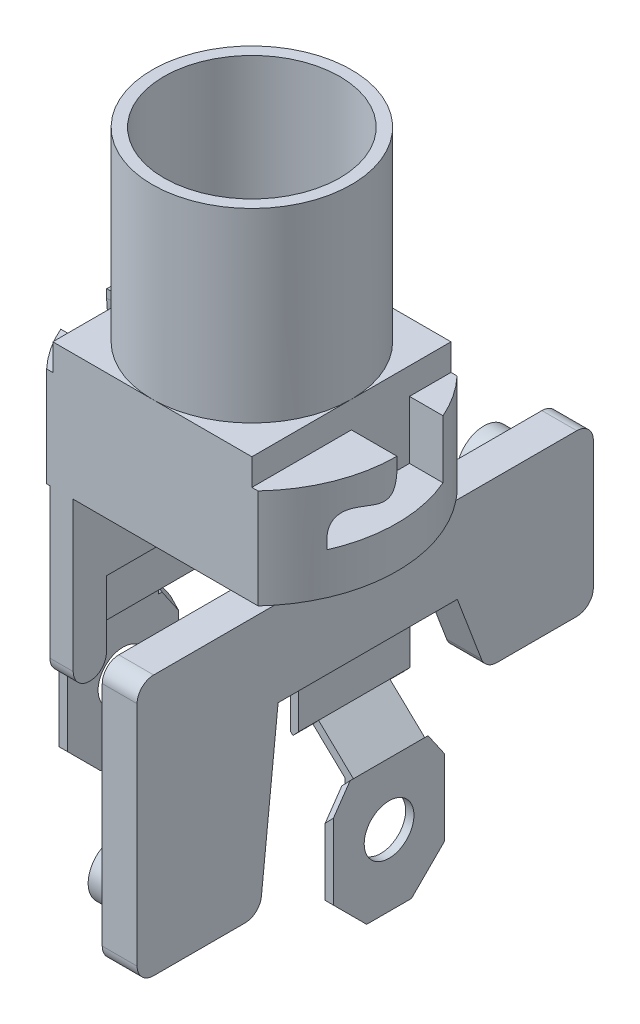
SolidWorks part; units mm, degrees
ref_plane "Front Plane" through (0, 0, 0) normal (0, 0, 1) x (1, 0, 0)
ref_plane "Top Plane" through (0, 0, 0) normal (0, 1, 0) x (1, 0, 0)
ref_plane "Right Plane" through (0, 0, 0) normal (1, 0, 0) x (0, 0, -1)
sketch "Sketch1" plane through (0, 0, 0) normal (0, 1, 0) x (1, 0, 0)
  circle A0 centre (0, 0) radius 6
  circle A1 centre (0, 0) radius 5.3
  dimension "D1" = 12
  dimension "D2" = 0.7
extrude "Boss-Extrude1" add sketch "Sketch1" along normal blind 11.2
sketch "Sketch2" plane through (0, 0, 0) normal (0, -1, 0) x (1, 0, 0)
  line L1 (6, 6) -> (-6, 6)
  line L2 (6, 6) -> (6, -6)
  line L3 (6, -6) -> (-6, -6)
  line L4 (-6, 6) -> (-6, -6)
  line L5 (6, 6) -> (-6, -6) construction
  line L6 (6, -6) -> (-6, 6) construction
  circle A0 centre (0, 0) radius 6 construction
  point P0 (0, 0)
extrude "Boss-Extrude2" add sketch "Sketch2" along normal blind 1.6
sketch "Sketch3" plane through (0, -1.6, 0) normal (0, -1, 0) x (1, 0, 0)
  line L0 (-6, -6) -> (6, -6) construction
  line L1 (8.75, 6) -> (-8.75, 6)
  line L2 (8.75, 6) -> (8.75, -6)
  line L3 (8.75, -6) -> (-8.75, -6)
  line L4 (-8.75, 6) -> (-8.75, -6)
  line L5 (8.75, 6) -> (-8.75, -6) construction
  line L6 (8.75, -6) -> (-8.75, 6) construction
  point P0 (0, 0)
  dimension "D1" = 17.5
extrude "Boss-Extrude3" add sketch "Sketch3" along normal blind 6
sketch "Sketch4" plane through (-8.75, 0, 0) normal (-1, 0, 0) x (0, 0, 1)
  line L0 (3.5, -1.6) -> (3.5, -5.1)
  line L1 (6, -1.6) -> (-6, -1.6) construction
  line L2 (3.5, -5.1) -> (-3.5, -5.1)
  line L3 (-3.5, -5.1) -> (-3.5, -4.6)
  line L5 (0, -2.1) -> (0, -1.6)
  line L6 (6, -1.6) -> (-6, -1.6) construction
  line L7 (0, -1.6) -> (3.5, -1.6)
  spline S0 degree 3 poles (-3.5, -4.6) (-3.5, -3.6819) (-2.6363, -2.9315) (-0.6059, -3.976) (0, -3.2065) (0, -2.1) knots 0 0 0 0 0.30682 0.67372 1 1 1 1
  dimension "D1" = 3.5
  dimension "D2" = 7
  dimension "D3" = 1.5
  dimension "D4" = 3.5
  dimension "D5" = 1.8
  dimension "D6" = 0.5
  dimension "D7" = 0.5
extrude "Cut-Extrude1" cut sketch "Sketch4" against normal blind 2.75
pattern_circular "CirPattern8" count 2 over 360 about axis through (0, 11.2, 0) along (0, -1, 0) of "Cut-Extrude1"
sketch "Sketch5" plane through (0, 11.2, 0) normal (0, 1, 0) x (1, 0, 0)
  circle A0 centre (0, 0) radius 8.75
extrude "Cut-Extrude2" cut sketch "Sketch5" against normal through all flip side to cut
sketch "Sketch6" plane through (0, -7.6, 0) normal (0, -1, 0) x (1, 0, 0)
  line L0 (-6.3689, -6) -> (6.3689, -6) construction
  line L1 (-4.7689, 6) -> (-6.1689, 6)
  line L2 (-4.7689, 6) -> (-4.7689, -6)
  line L3 (-4.7689, -6) -> (-6.1689, -6)
  line L4 (-6.1689, 6) -> (-6.1689, -6)
  line L5 (-4.7689, 6) -> (-6.1689, -6) construction
  line L6 (-4.7689, -6) -> (-6.1689, 6) construction
  line L7 (-6.1689, 4.35) -> (-7.7689, 3)
  line L8 (-7.7689, 3) -> (-7.7689, -3)
  line L9 (-7.7689, -3) -> (-6.1689, -4.35)
  line L10 (6.3689, 6) -> (-6.3689, 6) construction
  point P0 (-5.4689, 0)
  point P9 (-7.7689, 0)
  line M8 (6.3689, 6) -> (-6.3689, 6)
  line M10 (-6.3689, -6) -> (6.3689, -6)
  dimension "D1" = 3
  dimension "D2" = 8.7
  dimension "D3" = 1.4
  dimension "D4" = 0.2
  dimension "D5" = 6
extrude "Boss-Extrude4" add sketch "Sketch6" along normal blind 5 contours L8 L9 L4 L7 | L4 L2 M8 M10 region at (-5.4689, -7.6, 0) region at (-6.9199, -7.6, 0)
sketch "Sketch7" plane through (0, -12.6, 0) normal (0, -1, 0) x (1, 0, 0)
  line L0 (-4.7689, 6) -> (-4.7689, -6) construction
  line L1 (-6.1689, 6) -> (-4.7689, 6)
  line L2 (-6.1689, 6) -> (-6.1689, 4)
  line L3 (-6.1689, 4) -> (-4.7689, 4)
  line L4 (-4.7689, 6) -> (-4.7689, 4)
  line L5 (9.625, 0) -> (-9.625, 0) construction
  line L6 (-4.7689, -6) -> (-4.7689, -4)
  line L7 (-6.1689, -4) -> (-4.7689, -4)
  line L8 (-6.1689, -6) -> (-6.1689, -4)
  line L9 (-6.1689, -6) -> (-4.7689, -6)
  dimension "D1" = 2
extrude "Boss-Extrude5" add sketch "Sketch7" along normal blind 5
sketch "Sketch8" plane through (0, -7.6, 0) normal (0, -1, 0) x (1, 0, 0)
  line L0 (-4.7689, 6) -> (-4.7689, -6) construction
  line L1 (6.8311, 13.75) -> (4.7311, 13.75)
  line L2 (6.8311, 13.75) -> (6.8311, -13.75)
  line L3 (6.8311, -13.75) -> (4.7311, -13.75)
  line L4 (4.7311, 13.75) -> (4.7311, -13.75)
  line L5 (6.8311, 13.75) -> (4.7311, -13.75) construction
  line L6 (6.8311, -13.75) -> (4.7311, 13.75) construction
  point P0 (5.7811, 0)
  point P5 (6.8311, 0)
  dimension "D1" = 27.5
  dimension "D2" = 2.1
  dimension "D3" = 9.5
extrude "Boss-Extrude6" add sketch "Sketch8" along normal blind 15.7
sketch "Sketch9" plane through (6.8311, 0, 0) normal (1, 0, 0) x (0, 0, -1)
  line L0 (-6.35, -23.3) -> (-5.25, -12.8)
  line L1 (13.75, -23.3) -> (-13.75, -23.3) construction
  line L2 (-5.25, -12.8) -> (5.55, -12.8)
  line L3 (5.55, -12.8) -> (7.25, -17.3)
  line L4 (7.25, -17.3) -> (13.75, -17.3)
  line L5 (13.75, -23.3) -> (13.75, -7.6) construction
  line L6 (13.75, -17.3) -> (13.75, -23.3)
  line L7 (13.75, -23.3) -> (-6.35, -23.3)
  line L8 (-13.75, -23.3) -> (-13.75, -7.6) construction
  line L9 (-5.4679, -7.6) -> (-13.75, -7.6) construction
  line L10 (13.75, -7.6) -> (5.4679, -7.6) construction
  dimension "D1" = 7.4
  dimension "D2" = 5.2
  dimension "D3" = 8.5
  dimension "D4" = 8.2
  dimension "D5" = 9.7
  dimension "D6" = 6.5
extrude "Cut-Extrude3" cut sketch "Sketch9" against normal blind 3
fillet "Fillet1" radius 1 10 edges at (5.7811, -7.6, 13.75) (5.7811, -7.6, -13.75) (-5.4689, -17.6, -6) (-5.4689, -17.6, -4) (-5.4689, -17.6, 6) (-5.4689, -17.6, 4) (5.7811, -23.3, 13.75) (5.7811, -23.3, 6.35) (5.7811, -17.3, -7.25) (5.7811, -17.3, -13.75)
sketch "Sketch11" plane through (0, 0, 0) normal (0, 0, 1) x (1, 0, 0)
  line L0 (-6.1689, -12.6) -> (-6.1689, -15.5998)
  line L1 (-6.1689, -16.6) -> (-6.1689, -7.6) construction
  line L2 (-6.1689, -15.5998) -> (-8.2689, -17.5998)
  line L3 (-8.2689, -17.5998) -> (-8.2689, -25.5998)
  line L4 (-8.2689, -25.5998) -> (-7.7689, -25.5998)
  line L5 (-7.7689, -25.5998) -> (-7.7689, -17.8141)
  line L6 (-7.7689, -17.8141) -> (-5.6689, -15.8141)
  line L7 (-5.6689, -15.8141) -> (-5.6689, -12.6)
  line L8 (-5.6689, -12.6) -> (-6.1689, -12.6)
  dimension "D1" = 0.5
  dimension "D2" = 0.5
  dimension "D3" = 0.5
  dimension "D4" = 8
  dimension "D5" = 2.6
  dimension "D6" = 2
extrude "Boss-Extrude7" add sketch "Sketch11" along normal mid plane 6.7
sketch "Sketch12" plane through (4.8566, -5.0994, 0) normal (-0.6897, 0.7241, 0) x (0.7241, 0.6897, 0)
  line L0 (-18.1256, 0) -> (-15.2256, 0) construction
  line L1 (-18.1256, -3.35) -> (-18.1256, 3.35) construction
  line L2 (-15.2256, -3.35) -> (-15.2256, 3.35) construction
  line L4 (-15.2256, 2.15) -> (-18.1256, 2.15)
  line L5 (-15.2256, 2.15) -> (-15.2256, -2.15)
  line L6 (-15.2256, -2.15) -> (-18.1256, -2.15)
  line L7 (-18.1256, 2.15) -> (-18.1256, -2.15)
  line L8 (-15.2256, 2.15) -> (-18.1256, -2.15) construction
  line L9 (-15.2256, -2.15) -> (-18.1256, 2.15) construction
  line L10 (-15.2256, 3.35) -> (-18.1256, 3.35)
  line L11 (-15.2256, 3.35) -> (-15.2256, -3.35)
  line L12 (-15.2256, -3.35) -> (-18.1256, -3.35)
  line L13 (-18.1256, 3.35) -> (-18.1256, -3.35)
  line L14 (-15.2256, 3.35) -> (-18.1256, -3.35) construction
  line L15 (-15.2256, -3.35) -> (-18.1256, 3.35) construction
  point P6 (-16.6756, 0)
  point P11 (-16.6756, 0)
  line M2 (-15.2256, 3.35) -> (-18.1256, 3.35)
  line M3 (-18.1256, 3.35) -> (-18.1256, -3.35)
  line M4 (-18.1256, -3.35) -> (-15.2256, -3.35)
  line M5 (-15.2256, -3.35) -> (-15.2256, 3.35)
  dimension "D1" = 4.3
extrude "Cut-Extrude4" cut sketch "Sketch12" against normal blind 6.7 contours L4 M5 M2 M3 | L6 M5 M3 M4 region at (-7.2189, -16.5998, -2.75) region at (-7.2189, -16.5998, 2.75)
chamfer "Chamfer1" distance 1 angle 45 2 edges at (-8.0189, -17.8623, 3.35) (-8.0189, -17.8623, -3.35)
chamfer "Chamfer2" distance 2 angle 45 2 edges at (-8.0189, -25.5998, -3.35) (-8.0189, -25.5998, 3.35)
sketch "Sketch13" plane through (-8.2689, 0, 0) normal (-1, 0, 0) x (0, 0, 1)
  line L0 (3.35, -19.0498) -> (3.35, -23.5998) construction
  line L1 (2.15, -17.5998) -> (-2.15, -17.5998) construction
  circle A0 centre (0, -21.3248) radius 1.5
  point P5 (3.35, -21.3248)
  point P8 (0, -17.5998)
  dimension "D1" = 3
extrude "Cut-Extrude5" cut sketch "Sketch13" against normal blind 6.7
mirror "Mirror3" about plane through (0, 0, 0) normal (1, 0, 0) of "Cut-Extrude5", "Chamfer2", "Chamfer1", "Cut-Extrude4", "Boss-Extrude7"
sketch "Sketch14" plane through (4.7311, 0, 0) normal (-1, 0, 0) x (0, 0, 1)
  line L0 (10.65, -20.6) -> (11.25, -20.6) construction
  circle A0 centre (-11.25, -10.3) radius 1.65
  circle A1 centre (10.95, -20.6) radius 1.65
  dimension "D1" = 3.3
extrude "Boss-Extrude8" add sketch "Sketch14" along normal blind 2
